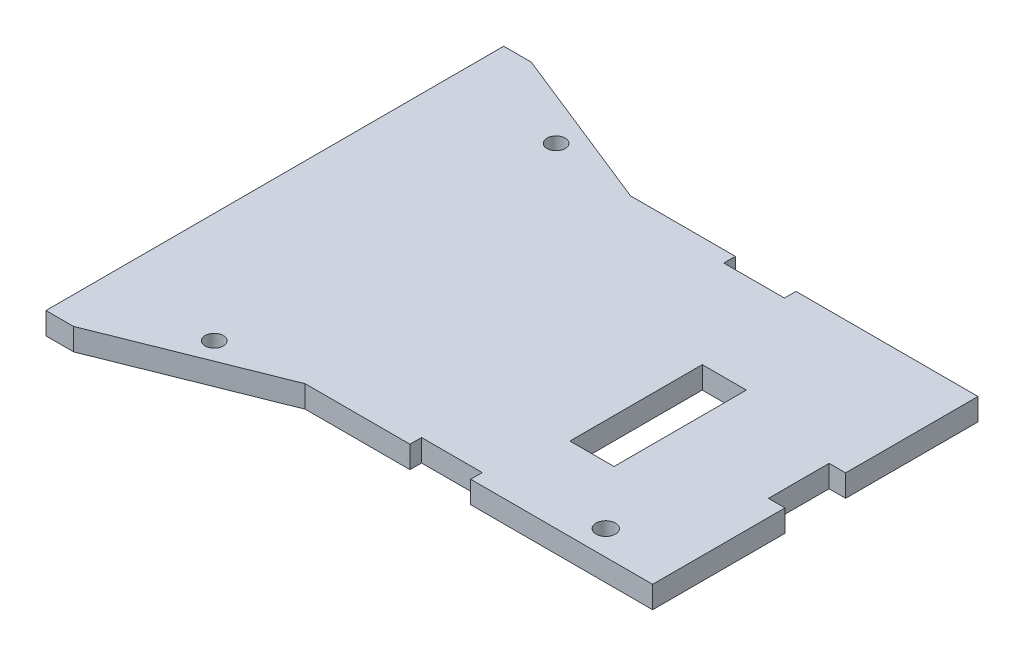
SolidWorks part; units mm, degrees
material "Acrylic (Medium-high impact)"
ref_plane "Front" through (0, 0, 0) normal (0, 0, 1) x (1, 0, 0)
ref_plane "Top" through (0, 0, 0) normal (0, 1, 0) x (1, 0, 0)
ref_plane "Right" through (0, 0, 0) normal (1, 0, 0) x (0, 0, -1)
sketch "Sketch1" plane through (0, 0, 0) normal (0, 1, 0) x (1, 0, 0)
  line L1 (30, 0) -> (93, 0)
  line L3 (30, 59) -> (93, 59)
  line L4 (93, 0) -> (93, 59)
  line L5 (0, -12) -> (-5, -12)
  line L7 (0, 71) -> (-5, 71)
  line L8 (-5, -12) -> (-5, 71)
  line L9 (0, 71) -> (30, 59)
  line L10 (30, 0) -> (0, -12)
  point P6 (0, 0)
  dimension "D2" = 59
  dimension "D3" = 5
extrude "Boss-Extrude1" add sketch "Sketch1" along normal blind 4
sketch "Sketch3" plane through (0, 0, 0) normal (0, -1, 0) x (1, 0, 0)
  line L0 (37.2411, -11.7625) -> (37.2411, -46.0104) construction
  line L1 (-1.5096, -2.8751) -> (-1.5096, 12.6038) construction
  line L2 (-1.5096, -37.3753) -> (-1.5096, -29.0949) construction
  line L3 (-1.5096, -25.3684) -> (-1.5096, -19.9005) construction
  line L4 (-1.2855, -63.7014) -> (-1.2855, -55.9809) construction
  line L5 (-1.5096, -51.4436) -> (-1.5096, -43.5757) construction
  line L6 (-1.5096, -14.7625) -> (-1.5096, -6.2262) construction
  line L7 (0, 12) -> (30, 0) construction
  line L8 (54.8078, -36.3846) -> (79.1499, -36.3846) construction
  line L9 (84.0769, -52.4436) -> (84.0769, -37.3753) construction
  line L10 (73.3749, -14.6495) -> (73.3749, -3.2262) construction
  line L11 (79.1499, -22.0574) -> (79.1499, -5.2937) construction
  line L12 (30, 0) -> (93, 0) construction
  line L13 (93, 0) -> (93, -59) construction
  circle A0 centre (84.8469, -55.4703) radius 1
  circle A1 centre (74, -5) radius 1
  circle A2 centre (71, -5) radius 1
  text T0 "Rocket\r\nLogger" font "Calibri" height 5.5
  text T1 "V1" font "Arial" height 4
  text T2 "V3" font "Arial" height 4
  text T3 "V4" font "Arial" height 4
  text T4 "I1" font "Arial" height 4
  text T5 "I2" font "Arial" height 4
  text T6 "V2" font "Arial" height 4
  text T7 "GND\r\nDI 6\r\nDI 5\r\nDI 4\r\nDI 3\r\nDI 2\r\nDI 1" font "Arial" height 2
  text T8 "POWER" font "Arial" height 2
  text T9 "STAT\r\nERR" font "Arial" height 2
  text T10 "start / stop" font "Arial" height 2
  point P27 (0, 0)
  dimension "D1" = 2
  dimension "D2" = 2
  dimension "D3" = 2
  dimension "D4" = 5
  dimension "D5" = 0
  dimension "D6" = 3
  dimension "D7" = 19
extrude "Cut-Extrude2" cut sketch "Sketch3" against normal blind 1
sketch "Sketch5" plane through (0, 0, 0) normal (0, -1, 0) x (1, 0, 0)
  line L0 (93, 0) -> (93, -59) construction
  line L1 (71, -39) -> (63, -39)
  line L2 (71, -39) -> (71, -15)
  line L3 (71, -15) -> (63, -15)
  line L4 (63, -39) -> (63, -15)
  line L5 (93, -59) -> (30, -59) construction
  line L6 (30, 0) -> (93, 0) construction
  dimension "D1" = 24
  dimension "D2" = 8
  dimension "D3" = 22
  dimension "D4" = 20
  dimension "D5" = 15
extrude "Cut-Extrude4" cut sketch "Sketch5" against normal through all
sketch "Sketch6" plane through (0, 4, 0) normal (0, 1, 0) x (1, 0, 0)
  line L0 (93, 0) -> (93, 59) construction
  line L2 (30, 0) -> (93, 0) construction
  circle A0 centre (80, 4.5) radius 1.75
  point P6 (83.7103, 0)
  dimension "D1" = 3.5
  dimension "D2" = 13
  dimension "D3" = 4.5
extrude "Cut-Extrude5" cut sketch "Sketch6" against normal through all
sketch "Sketch7" plane through (0, 4, 0) normal (0, 1, 0) x (1, 0, 0)
  line L0 (93, 59) -> (30, 59) construction
  line L2 (30, 0) -> (93, 0) construction
  line L3 (-5, 71) -> (-5, -12) construction
  circle A0 centre (15, 60.5) radius 1.65
  circle A1 centre (15, -1.5) radius 1.65
  dimension "D1" = 3.3
  dimension "D4" = 20
  dimension "D6" = 3.3
  dimension "D2" = 1.5
  dimension "D3" = 20
  dimension "D5" = 1.5
extrude "Cut-Extrude6" cut sketch "Sketch7" against normal through all
sketch "Sketch8" plane through (0, 4, 0) normal (0, 1, 0) x (1, 0, 0)
  line L0 (93, 0) -> (93, 59) construction
  line L1 (93, 35) -> (90, 35)
  line L2 (93, 35) -> (93, 24)
  line L3 (93, 24) -> (90, 24)
  line L4 (90, 35) -> (90, 24)
  line L5 (93, 59) -> (30, 59) construction
  line L6 (60, 59) -> (49, 59)
  line L7 (60, 59) -> (60, 56.9)
  line L8 (60, 56.9) -> (49, 56.9)
  line L9 (49, 59) -> (49, 56.9)
  line L10 (30, 0) -> (93, 0) construction
  line L11 (60, 0) -> (49, 0)
  line L12 (60, 0) -> (60, 2.1)
  line L13 (60, 2.1) -> (49, 2.1)
  line L14 (49, 0) -> (49, 2.1)
  dimension "D1" = 2.1
  dimension "D2" = 2.1
  dimension "D3" = 11
  dimension "D4" = 11
  dimension "D5" = 11
  dimension "D6" = 3
  dimension "D7" = 33
  dimension "D8" = 33
  dimension "D9" = 24
  dimension "D10" = 24
extrude "Cut-Extrude7" cut sketch "Sketch8" against normal through all
